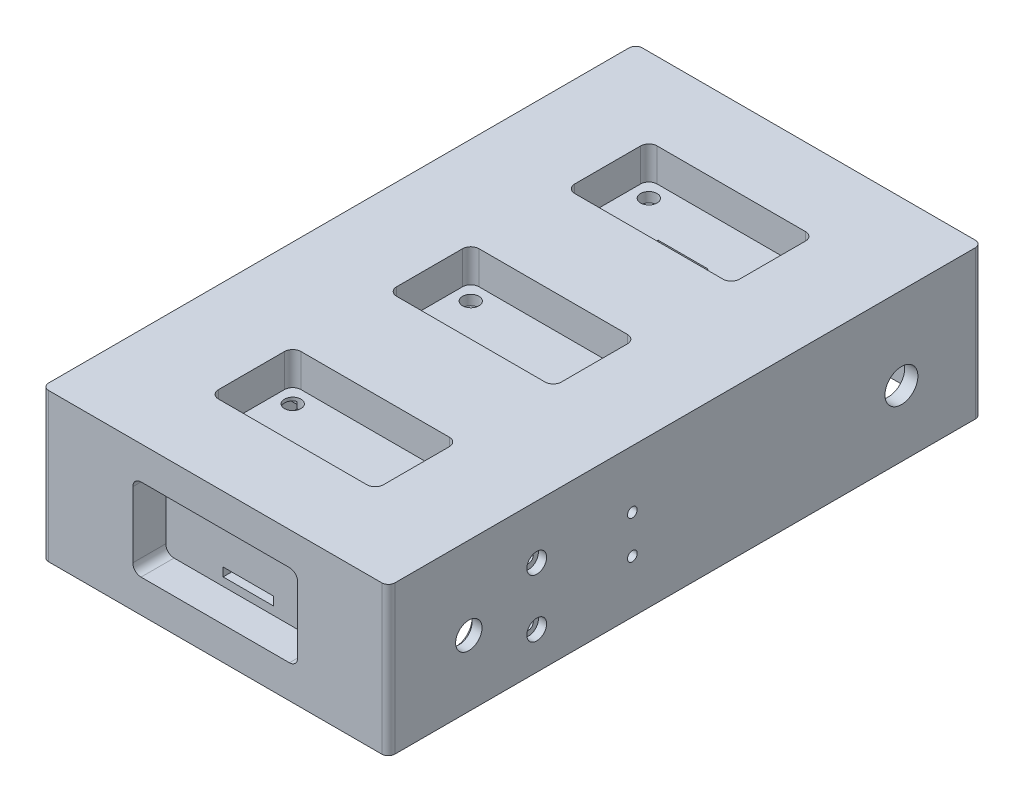
SolidWorks part; units mm, degrees
ref_plane "Спереди" through (0, 0, 0) normal (0, 0, 1) x (1, 0, 0)
ref_plane "Сверху" through (0, 0, 0) normal (0, 1, 0) x (1, 0, 0)
ref_plane "Справа" through (0, 0, 0) normal (1, 0, 0) x (0, 0, -1)
sketch "Эскиз1" plane through (0, 0, 0) normal (0, 1, 0) x (1, 0, 0)
  line L1 (-52.5, -90) -> (52.5, -90)
  line L2 (-52.5, -90) -> (-52.5, 90)
  line L3 (-52.5, 90) -> (52.5, 90)
  line L4 (52.5, -90) -> (52.5, 90)
  line L5 (-52.5, -90) -> (52.5, 90) construction
  line L6 (-52.5, 90) -> (52.5, -90) construction
  point P0 (0, 0)
  dimension "D1" = 105
  dimension "D2" = 180
extrude "Бобышка-Вытянуть1" add sketch "Эскиз1" along normal blind 45
sketch "Эскиз2" plane through (0, 0, 90) normal (0, 0, 1) x (1, 0, 0)
  line L0 (-1050, 22.5) -> (48950, 22.5) construction
  line L1 (-52.5, 45) -> (-52.5, 0) construction
  line L2 (0, -999.2777) -> (0, 49000.7223) construction
  line L4 (-22.5, 10) -> (22.5, 10)
  line L5 (-25, 12.5) -> (-25, 32.5)
  line L6 (-22.5, 35) -> (22.5, 35)
  line L7 (25, 12.5) -> (25, 32.5)
  line L8 (-25, 10) -> (25, 35) construction
  line L9 (-25, 35) -> (25, 10) construction
  arc A0 (-22.5, 35) -> (-25, 32.5) centre (-22.5, 32.5) ccw
  arc A1 (-25, 12.5) -> (-22.5, 10) centre (-22.5, 12.5) ccw
  arc A2 (25, 12.5) -> (22.5, 10) centre (22.5, 12.5) cw
  arc A3 (25, 32.5) -> (22.5, 35) centre (22.5, 32.5) ccw
  point P5 (-52.5, 22.5)
  point P6 (0, 22.5)
  dimension "D3" = 2.5
  dimension "D4" = 2.5
  dimension "D1" = 25
  dimension "D2" = 50
extrude "Вырез-Вытянуть1" cut sketch "Эскиз2" against normal blind 10
sketch "Эскиз4" plane through (0, 45, 0) normal (0, 1, 0) x (1, 0, 0)
  line L0 (0, -1000) -> (0, 49000) construction
  line L1 (-1000, 0) -> (49000, 0) construction
  line L2 (-22.5, 41.5) -> (22.5, 41.5)
  line L3 (-25, 44) -> (-25, 64)
  line L4 (-22.5, 66.5) -> (22.5, 66.5)
  line L5 (-22.5, -12.5) -> (22.5, -12.5)
  line L6 (-25, -10) -> (-25, 10)
  line L7 (-22.5, 12.5) -> (22.5, 12.5)
  line L8 (25, -10) -> (25, 10)
  line L9 (-25, -12.5) -> (25, 12.5) construction
  line L10 (-25, 12.5) -> (25, -12.5) construction
  line L11 (25, 44) -> (25, 64)
  line L12 (-25, 41.5) -> (25, 66.5) construction
  line L13 (-25, 66.5) -> (25, 41.5) construction
  line L14 (-25, -12.5) -> (25, -12.5) [skipped]
  line L15 (-25, -12.5) -> (-25, 12.5) [skipped]
  line L16 (-25, 12.5) -> (25, 12.5) [skipped]
  line L17 (25, -12.5) -> (25, 12.5) [skipped]
  line L18 (-25, -12.5) -> (25, 12.5) construction
  line L19 (-25, 12.5) -> (25, -12.5) construction
  line L20 (-22.5, -66.5) -> (22.5, -66.5)
  line L21 (-25, -64) -> (-25, -44)
  line L22 (-22.5, -41.5) -> (22.5, -41.5)
  line L23 (25, -64) -> (25, -44)
  line L24 (-25, -66.5) -> (25, -41.5) construction
  line L25 (-25, -41.5) -> (25, -66.5) construction
  arc A0 (22.5, -41.5) -> (25, -44) centre (22.5, -44) cw
  arc A1 (25, -64) -> (22.5, -66.5) centre (22.5, -64) cw
  arc A2 (-22.5, -66.5) -> (-25, -64) centre (-22.5, -64) cw
  arc A3 (-25, -44) -> (-22.5, -41.5) centre (-22.5, -44) cw
  arc A4 (-25, 64) -> (-22.5, 66.5) centre (-22.5, 64) cw
  arc A5 (-22.5, 12.5) -> (-25, 10) centre (-22.5, 10) ccw
  arc A6 (25, -10) -> (22.5, -12.5) centre (22.5, -10) cw
  arc A7 (22.5, 66.5) -> (25, 64) centre (22.5, 64) cw
  arc A8 (25, 44) -> (22.5, 41.5) centre (22.5, 44) cw
  arc A9 (-22.5, 41.5) -> (-25, 44) centre (-22.5, 44) cw
  arc A10 (22.5, 12.5) -> (25, 10) centre (22.5, 10) cw
  arc A11 (-22.5, -12.5) -> (-25, -10) centre (-22.5, -10) cw
  point P8 (0, 0)
  point P9 (0, 54)
  point P18 (0, 0)
  point P23 (0, -54)
  dimension "D7" = 2.5
  dimension "D8" = 2.5
  dimension "D1" = 25
  dimension "D2" = 50
  dimension "D5" = 41.5
  dimension "D6" = 41.5
  dimension "D3" = 2
  dimension "D4" = 2
extrude "Вырез-Вытянуть2" cut sketch "Эскиз4" against normal blind 10
mirror "Зеркальное отражение1" about plane through (0, 0, 0) normal (0, 0, 1) of "Вырез-Вытянуть1"
shell "Оболочка1" thickness 4 removed face at (0, 0, 0)
sketch "Эскиз5" plane through (-52.5, 0, 0) normal (-1, 0, 0) x (0, 0, 1)
  line L0 (45, 28.75) -> (45, 11.25) construction
  line L2 (90, 45) -> (90, 0) construction
  line L4 (-90, 0) -> (90, 0) construction
  line L7 (-1075, 20) -> (48925, 20) construction
  line L8 (-90, 45) -> (-90, 0) construction
  circle A3 centre (45, 28.75) radius 1.45
  circle A4 centre (45, 11.25) radius 1.45
  circle A5 centre (65.6, 20) radius 4
  circle A6 centre (-65.6, 20) radius 5
  dimension "D2" = 17.5
  dimension "D3" = 20
  dimension "D6" = 10
  dimension "D1" = 17.5
  dimension "D5" = 2.9
  dimension "D9" = 45
  dimension "D10" = 20.6
  dimension "D11" = 8
  dimension "D4" = 24.4
extrude "Вырез-Вытянуть3" cut sketch "Эскиз5" against normal blind 15
sketch "Эскиз6" plane through (-52.5, 0, 0) normal (-1, 0, 0) x (0, 0, 1)
  circle A2 centre (45, 28.75) radius 3
  circle A3 centre (45, 11.25) radius 3
  dimension "D1" = 6
extrude "Вырез-Вытянуть4" cut sketch "Эскиз6" against normal blind 2.5
sketch "Эскиз10" plane through (0, 31, 0) normal (0, -1, 0) x (-1, 0, 0)
  line L1 (21, -42) -> (26, -42)
  line L2 (21, -42) -> (21, -78.5)
  line L3 (21, -78.5) -> (26, -78.5)
  line L4 (26, -42) -> (26, -78.5)
  line L5 (21, -42) -> (26, -78.5) construction
  line L6 (21, -78.5) -> (26, -42) construction
  line L7 (29, -44) -> (29, -64) construction
  line L8 (22.5, -70.5) -> (-22.5, -70.5) construction
  point P4 (23.5, -60.25)
  dimension "D1" = 36.5
  dimension "D2" = 3
  dimension "D3" = 5
  dimension "D4" = 8
extrude "Вырез-Вытянуть15" cut sketch "Эскиз10" against normal blind 3 and the other way through all
sketch "Эскиз11" plane through (-48.5, 0, 0) normal (1, 0, 0) x (0, 0, -1)
  circle A1 centre (-65.6, 20) radius 5
  dimension "D1" = 10
extrude "Вырез-Вытянуть16" cut sketch "Эскиз11" against normal blind 1
mirror "Зеркальное отражение2" about plane through (0, 0, 0) normal (1, 0, 0) of "Вырез-Вытянуть16", "Вырез-Вытянуть15", "Вырез-Вытянуть4", "Вырез-Вытянуть3"
sketch "Эскиз12" plane through (0, 6, 0) normal (0, -1, 0) x (-1, 0, 0)
  line L0 (-1014.7864, -78) -> (48985.2136, -78) construction
  line L1 (21, -76) -> (-21, -76) construction
  line L2 (0, -1061) -> (0, 48939) construction
  line L3 (-10, -1061) -> (-10, 48939) construction
  line L4 (10, -1061) -> (10, 48939) construction
  circle A0 centre (-10, -78) radius 1.45
  circle A1 centre (10, -78) radius 1.45
  point P7 (0, -76)
  dimension "D4" = 2.9
  dimension "D1" = 2
  dimension "D2" = 20
  dimension "D3" = 10
extrude "Вырез-Вытянуть17" cut sketch "Эскиз12" against normal blind 14
sketch "Эскиз25" plane through (0, 31, 0) normal (0, -1, 0) x (1, 0, 0)
  line L0 (22.5, 37.5) -> (-22.5, 37.5) construction
  line L1 (-12.5, 37.5) -> (12.5, 37.5)
  line L2 (-12.5, 37.5) -> (-12.5, 16.5)
  line L3 (-12.5, 16.5) -> (12.5, 16.5)
  line L4 (12.5, 37.5) -> (12.5, 16.5)
  line L5 (-12.5, 37.5) -> (12.5, 16.5) construction
  line L6 (-12.5, 16.5) -> (12.5, 37.5) construction
  line L7 (-22.5, 16.5) -> (22.5, 16.5) construction
  point P4 (0, 27)
  dimension "D1" = 25
extrude "Бобышка-Вытянуть2" add sketch "Эскиз25" against normal up to surface (10 mm away) up to face at (0, 41, 54)
sketch "Эскиз13" plane through (0, 31, 0) normal (0, -1, 0) x (-1, 0, 0)
  line L0 (-1008.6674, -32.5) -> (48991.3326, -32.5) construction
  line L2 (0, -1027.5) -> (0, 48972.5) construction
  line L4 (-22.5, -37.5) -> (-12.5, -37.5) construction
  circle A0 centre (-9, -32.5) radius 1.45
  circle A1 centre (9, -32.5) radius 1.45
  dimension "D2" = 18
  dimension "D3" = 2.9
  dimension "D1" = 5
  dimension "D4" = 18
extrude "Вырез-Вытянуть18" cut sketch "Эскиз13" against normal blind 10
sketch "Эскиз14" plane through (0, 31, 0) normal (0, -1, 0) x (-1, 0, 0)
  line L0 (20, -957.2029) -> (20, 49042.7971) construction
  line L1 (29, 64) -> (29, 44) construction
  line L2 (-22.5, 70.5) -> (22.5, 70.5) construction
  line L3 (0, -972.5) -> (0, 49027.5) construction
  line L4 (22.5, 37.5) -> (-22.5, 37.5) construction
  line L5 (-20, -957.2029) -> (-20, 49042.7971) construction
  circle A0 centre (20, 45.5) radius 1.45
  circle A1 centre (20, -9.5) radius 1.45
  circle A2 centre (-20, -9.5) radius 1.45
  circle A3 centre (-20, 45.5) radius 1.45
  point P15 (0, 37.5)
  dimension "D1" = 2.9
  dimension "D3" = 9
  dimension "D2" = 55
  dimension "D4" = 25
extrude "Вырез-Вытянуть19" cut sketch "Эскиз14" against normal blind 3
sketch "Эскиз15" plane through (0, 35, 0) normal (0, 1, 0) x (1, 0, 0)
  line L0 (-1010.1672, -64) -> (48989.8328, -64) construction
  line L1 (0, -1031.5) -> (0, 48968.5) construction
  line L2 (-7.6, -65.3) -> (7.6, -65.3)
  line L3 (-7.6, -65.3) -> (-7.6, -62.7)
  line L4 (-7.6, -62.7) -> (7.6, -62.7)
  line L5 (7.6, -65.3) -> (7.6, -62.7)
  line L6 (-7.6, -65.3) -> (7.6, -62.7) construction
  line L7 (-7.6, -62.7) -> (7.6, -65.3) construction
  line L8 (22.5, -41.5) -> (-22.5, -41.5) construction
  line L9 (-22.5, -66.5) -> (22.5, -66.5) construction
  line L10 (-7.6, -10) -> (7.6, -10)
  line L11 (-7.6, -10) -> (-7.6, -7.4)
  line L12 (-7.6, -7.4) -> (7.6, -7.4)
  line L13 (7.6, -10) -> (7.6, -7.4)
  line L14 (-7.6, -10) -> (7.6, -7.4) construction
  line L15 (-7.6, -7.4) -> (7.6, -10) construction
  line L16 (-7.6, 45.3) -> (7.6, 45.3)
  line L17 (-7.6, 45.3) -> (-7.6, 47.9)
  line L18 (-7.6, 47.9) -> (7.6, 47.9)
  line L19 (7.6, 45.3) -> (7.6, 47.9)
  line L20 (-7.6, 45.3) -> (7.6, 47.9) construction
  line L21 (-7.6, 47.9) -> (7.6, 45.3) construction
  line L22 (-22.5, -12.5) -> (22.5, -12.5) construction
  line L23 (22.5, 12.5) -> (-22.5, 12.5) construction
  line L24 (-7.6, -61.3) -> (7.6, -61.3)
  line L25 (-7.6, -61.3) -> (-7.6, -58.7)
  line L26 (-7.6, -58.7) -> (7.6, -58.7)
  line L27 (7.6, -61.3) -> (7.6, -58.7)
  line L28 (-7.6, -61.3) -> (7.6, -58.7) construction
  line L29 (-7.6, -58.7) -> (7.6, -61.3) construction
  line L30 (-7.6, -6) -> (7.6, -6)
  line L31 (-7.6, -6) -> (-7.6, -3.4)
  line L32 (-7.6, -3.4) -> (7.6, -3.4)
  line L33 (7.6, -6) -> (7.6, -3.4)
  line L34 (-7.6, -6) -> (7.6, -3.4) construction
  line L35 (-7.6, -3.4) -> (7.6, -6) construction
  line L36 (-7.6, 49.3) -> (7.6, 49.3)
  line L37 (-7.6, 49.3) -> (-7.6, 51.9)
  line L38 (-7.6, 51.9) -> (7.6, 51.9)
  line L39 (7.6, 49.3) -> (7.6, 51.9)
  line L40 (-7.6, 49.3) -> (7.6, 51.9) construction
  line L41 (-7.6, 51.9) -> (7.6, 49.3) construction
  circle A0 centre (-20, -46.5) radius 2.5
  circle A1 centre (20, -46.5) radius 2.5
  circle A2 centre (-20, 7.5) radius 2.5
  circle A3 centre (20, 7.5) radius 2.5
  circle A4 centre (-20, 61.5) radius 2.5
  circle A5 centre (20, 61.5) radius 2.5
  point P1 (0, -64)
  point P12 (0, -41.5)
  point P16 (0, -8.7)
  point P21 (0, 46.6)
  point P41 (0, -4.7)
  point P42 (0, -60)
  point P51 (0, 50.6)
  dimension "D6" = 40
  dimension "D8" = 5
  dimension "D1" = 2.6
  dimension "D2" = 15.2
  dimension "D3" = 2.5
  dimension "D4" = 3
  dimension "D5" = 2.5
  dimension "D7" = 40
  dimension "D9" = 5
  dimension "D10" = 3
  dimension "D11" = 5
  dimension "D13" = 4
  dimension "D15" = 4
  dimension "D12" = 2
  dimension "D14" = 3
extrude "Вырез-Вытянуть20" cut sketch "Эскиз15" against normal blind 3
sketch "Эскиз16" plane through (0, 32, 0) normal (0, 1, 0) x (1, 0, 0)
  line L0 (-7.6, -64) -> (7.6, -64) construction
  line L1 (-7.6, -62.7) -> (-7.6, -65.3) construction
  line L2 (7.6, -65.3) -> (7.6, -62.7) construction
  line L3 (0, -1000) -> (0, 49000) construction
  line L4 (-7, -64.9) -> (7, -64.9)
  line L5 (-7, -64.9) -> (-7, -63.1)
  line L6 (-7, -63.1) -> (7, -63.1)
  line L7 (7, -64.9) -> (7, -63.1)
  line L8 (-7, -64.9) -> (7, -63.1) construction
  line L9 (-7, -63.1) -> (7, -64.9) construction
  line L10 (-7, -9.6) -> (7, -9.6)
  line L11 (-7, -9.6) -> (-7, -7.8)
  line L12 (-7, -7.8) -> (7, -7.8)
  line L13 (7, -9.6) -> (7, -7.8)
  line L14 (-7.6, -8.7) -> (7.6, -8.7) construction
  line L15 (-7, -9.6) -> (7, -7.8) construction
  line L16 (-7, -7.8) -> (7, -9.6) construction
  line L17 (-7, 45.7) -> (7, 45.7)
  line L18 (-7, 45.7) -> (-7, 47.5)
  line L19 (-7, 47.5) -> (7, 47.5)
  line L20 (7, 45.7) -> (7, 47.5)
  line L21 (-7.6, 46.6) -> (7.6, 46.6) construction
  line L22 (-7, 45.7) -> (7, 47.5) construction
  line L23 (-7, 47.5) -> (7, 45.7) construction
  line L24 (-7.6, -7.4) -> (-7.6, -10) construction
  line L25 (-7.6, -60) -> (7.6, -60) construction
  line L26 (-7, -60.9) -> (7, -60.9)
  line L27 (-7, -60.9) -> (-7, -59.1)
  line L28 (-7, -59.1) -> (7, -59.1)
  line L29 (7, -60.9) -> (7, -59.1)
  line L30 (-7, -60.9) -> (7, -59.1) construction
  line L31 (-7, -59.1) -> (7, -60.9) construction
  line L32 (-7.6, -58.7) -> (-7.6, -61.3) construction
  line L33 (7.6, -61.3) -> (7.6, -58.7) construction
  line L34 (-7.6, -4.7) -> (7.6, -4.7) construction
  line L35 (-7.6, -3.4) -> (-7.6, -6) construction
  line L36 (7.6, -6) -> (7.6, -3.4) construction
  line L37 (-7.6, -10) -> (7.6, -10) construction
  line L38 (-7, -5.6) -> (7, -5.6)
  line L39 (-7, -5.6) -> (-7, -3.8)
  line L40 (-7, -3.8) -> (7, -3.8)
  line L41 (7, -5.6) -> (7, -3.8)
  line L42 (-7, -5.6) -> (7, -3.8) construction
  line L43 (-7, -3.8) -> (7, -5.6) construction
  line L44 (7.6, -10) -> (7.6, -7.4) construction
  line L45 (-7.6, 47.9) -> (-7.6, 45.3) construction
  line L46 (7.6, 45.3) -> (7.6, 47.9) construction
  line L47 (-7.6, 45.3) -> (7.6, 45.3) construction
  line L48 (-7.6, 50.6) -> (7.6, 50.6) construction
  line L49 (-7.6, 51.9) -> (-7.6, 49.3) construction
  line L50 (7.6, 49.3) -> (7.6, 51.9) construction
  line L52 (-7, 49.7) -> (7, 49.7)
  line L53 (-7, 49.7) -> (-7, 51.5)
  line L54 (-7, 51.5) -> (7, 51.5)
  line L55 (7, 49.7) -> (7, 51.5)
  line L56 (-7, 49.7) -> (7, 51.5) construction
  line L57 (-7, 51.5) -> (7, 49.7) construction
  point P6 (0, -64)
  point P12 (0, -60)
  point P17 (0, -8.7)
  point P24 (0, 36.6)
  point P41 (0, -4.7)
  point P54 (0, 50.6)
  dimension "D1" = 1.8
  dimension "D2" = 14
  dimension "D4" = 0.4
  dimension "D3" = 0.4
extrude "Вырез-Вытянуть21" cut sketch "Эскиз16" against normal blind 3
sketch "Эскиз17" plane through (0, 0, 80) normal (0, 0, 1) x (1, 0, 0)
  line L0 (-7.6, 12.5) -> (7.6, 12.5)
  line L1 (-7.6, 12.5) -> (-7.6, 15.1)
  line L2 (-7.6, 15.1) -> (7.6, 15.1)
  line L3 (7.6, 12.5) -> (7.6, 15.1)
  line L4 (-7.6, 12.5) -> (7.6, 15.1) construction
  line L5 (-7.6, 15.1) -> (7.6, 12.5) construction
  line L8 (-22.5, 10) -> (22.5, 10) construction
  line L9 (0, -965) -> (0, 49035) construction
  line L10 (22.5, 35) -> (-22.5, 35) construction
  circle A0 centre (-20, 30) radius 2.5
  circle A1 centre (20, 30) radius 2.5
  point P0 (0, 13.8)
  point P20 (0, 35)
  dimension "D5" = 5
  dimension "D1" = 2.6
  dimension "D2" = 15.2
  dimension "D3" = 40
  dimension "D4" = 40
  dimension "D6" = 2.5
  dimension "D7" = 5
extrude "Вырез-Вытянуть22" cut sketch "Эскиз17" against normal blind 3
sketch "Эскиз18" plane through (0, 0, 77) normal (0, 0, 1) x (1, 0, 0)
  line L0 (-7.6, 13.8) -> (7.6, 13.8) construction
  line L1 (-7.6, 15.1) -> (-7.6, 12.5) construction
  line L2 (7.6, 12.5) -> (7.6, 15.1) construction
  line L4 (-7, 12.9) -> (7, 12.9)
  line L5 (-7, 12.9) -> (-7, 14.7)
  line L6 (-7, 14.7) -> (7, 14.7)
  line L7 (7, 12.9) -> (7, 14.7)
  line L8 (-7, 12.9) -> (7, 14.7) construction
  line L9 (-7, 14.7) -> (7, 12.9) construction
  point P6 (0, 13.8)
  dimension "D1" = 1.8
  dimension "D2" = 14
extrude "Вырез-Вытянуть23" cut sketch "Эскиз18" against normal blind 3
sketch "Эскиз19" plane through (0, 0, -80) normal (0, 0, -1) x (1, 0, 0)
  line L0 (-7.6, -32.5) -> (7.6, -32.5)
  line L1 (-7.6, -32.5) -> (-7.6, -29.9)
  line L2 (-7.6, -29.9) -> (7.6, -29.9)
  line L3 (7.6, -32.5) -> (7.6, -29.9)
  line L4 (-7.6, -32.5) -> (7.6, -29.9) construction
  line L5 (-7.6, -29.9) -> (7.6, -32.5) construction
  line L6 (0, -1010) -> (0, 48990) construction
  line L7 (-22.5, -10) -> (22.5, -10) construction
  line L10 (22.5, -35) -> (-22.5, -35) construction
  circle A0 centre (-20, -15) radius 2.5
  circle A1 centre (20, -15) radius 2.5
  point P0 (0, -31.2)
  point P14 (0, -10)
  dimension "D5" = 5
  dimension "D7" = 2.5
  dimension "D1" = 2.6
  dimension "D2" = 15.2
  dimension "D3" = 40
  dimension "D4" = 40
  dimension "D6" = 5
extrude "Вырез-Вытянуть24" cut sketch "Эскиз19" against normal blind 3
sketch "Эскиз20" plane through (0, 0, -77) normal (0, 0, -1) x (1, 0, 0)
  line L0 (-1007.6, -31.2) -> (48992.4, -31.2) construction
  line L1 (-7.6, -29.9) -> (-7.6, -32.5) construction
  line L3 (-7, -32.1) -> (7, -32.1)
  line L4 (-7, -32.1) -> (-7, -30.3)
  line L5 (-7, -30.3) -> (7, -30.3)
  line L6 (7, -32.1) -> (7, -30.3)
  line L7 (-7, -32.1) -> (7, -30.3) construction
  line L8 (-7, -30.3) -> (7, -32.1) construction
  line L10 (0, -1029.9) -> (0, 48970.1) construction
  line L11 (7.6, -29.9) -> (-7.6, -29.9) construction
  point P1 (0, -31.2)
  point P5 (-7.6, -31.2)
  point P18 (0, -29.9)
  dimension "D1" = 1.8
  dimension "D2" = 14
extrude "Вырез-Вытянуть25" cut sketch "Эскиз20" against normal blind 5
sketch "Эскиз21" plane through (0, 0, -90) normal (0, 0, -1) x (1, 0, 0)
  line L0 (-975, -22.5) -> (49025, -22.5) construction
  line L1 (37.75, -29.75) -> (47.25, -29.75)
  line L2 (37.75, -29.75) -> (37.75, -15.25)
  line L3 (37.75, -15.25) -> (47.25, -15.25)
  line L4 (47.25, -29.75) -> (47.25, -15.25)
  line L5 (37.75, -29.75) -> (47.25, -15.25) construction
  line L6 (37.75, -15.25) -> (47.25, -29.75) construction
  line L7 (25, -12.5) -> (25, -32.5) construction
  line L8 (42.5, -1022.5) -> (42.5, 48977.5) construction
  line L9 (52.5, -45) -> (52.5, 0) construction
  point P0 (42.5, -22.5)
  point P10 (25, -22.5)
  dimension "D1" = 9.5
  dimension "D2" = 14.5
  dimension "D3" = 10
extrude "Вырез-Вытянуть26" cut sketch "Эскиз21" against normal blind 4
sketch "Эскиз22" plane through (0, 0, 0) normal (0, -1, 0) x (-1, 0, 0)
  line L0 (-50.5, -925) -> (-50.5, 49075) construction
  line L2 (-52.5, -90) -> (-52.5, 90) construction
  line L3 (-1046.2998, 88) -> (48953.7002, 88) construction
  line L4 (-52.5, 90) -> (52.5, 90) construction
  line L5 (50.5, -925) -> (50.5, 49075) construction
  line L6 (52.5, 90) -> (52.5, -90) construction
  line L7 (-1052.5, -88) -> (48947.5, -88) construction
  line L8 (52.5, -90) -> (-52.5, -90) construction
  line L9 (0, -925) -> (0, 49075) construction
  line L10 (-1052.5, 0) -> (48947.5, 0) construction
  circle A0 centre (-50.5, -88) radius 1.425
  circle A1 centre (-50.5, 88) radius 1.425
  circle A2 centre (50.5, 88) radius 1.425
  circle A3 centre (50.5, -88) radius 1.425
  circle A4 centre (0, 88) radius 1.425
  circle A5 centre (0, -88) radius 1.425
  circle A6 centre (-50.5, 0) radius 1.425
  circle A7 centre (50.5, 0) radius 1.425
  point P27 (0, 90)
  point P34 (-52.5, 0)
  dimension "D5" = 2.85
  dimension "D1" = 2
  dimension "D2" = 2
  dimension "D3" = 2
  dimension "D4" = 2
extrude "Вырез-Вытянуть27" cut sketch "Эскиз22" against normal blind 9
sketch "Эскиз24" plane through (-52.5, 0, 0) normal (-1, 0, 0) x (0, 0, 1)
  line L0 (0, -1000) -> (0, 49000) construction
  line L1 (16, -988.2808) -> (16, 49011.7192) construction
  line L2 (-90, 0) -> (90, 0) construction
  circle A0 centre (16, 16) radius 1.475
  circle A1 centre (16, 27.5) radius 1.475
  dimension "D4" = 2.95
  dimension "D1" = 11.5
  dimension "D2" = 16
  dimension "D3" = 16
extrude "Вырез-Вытянуть28" cut sketch "Эскиз24" against normal through all
fillet "Скругление1" radius 2 4 edges at (52.5, 22.5, -90) (-52.5, 22.5, -90) (52.5, 22.5, 90) (-52.5, 22.5, 90)
